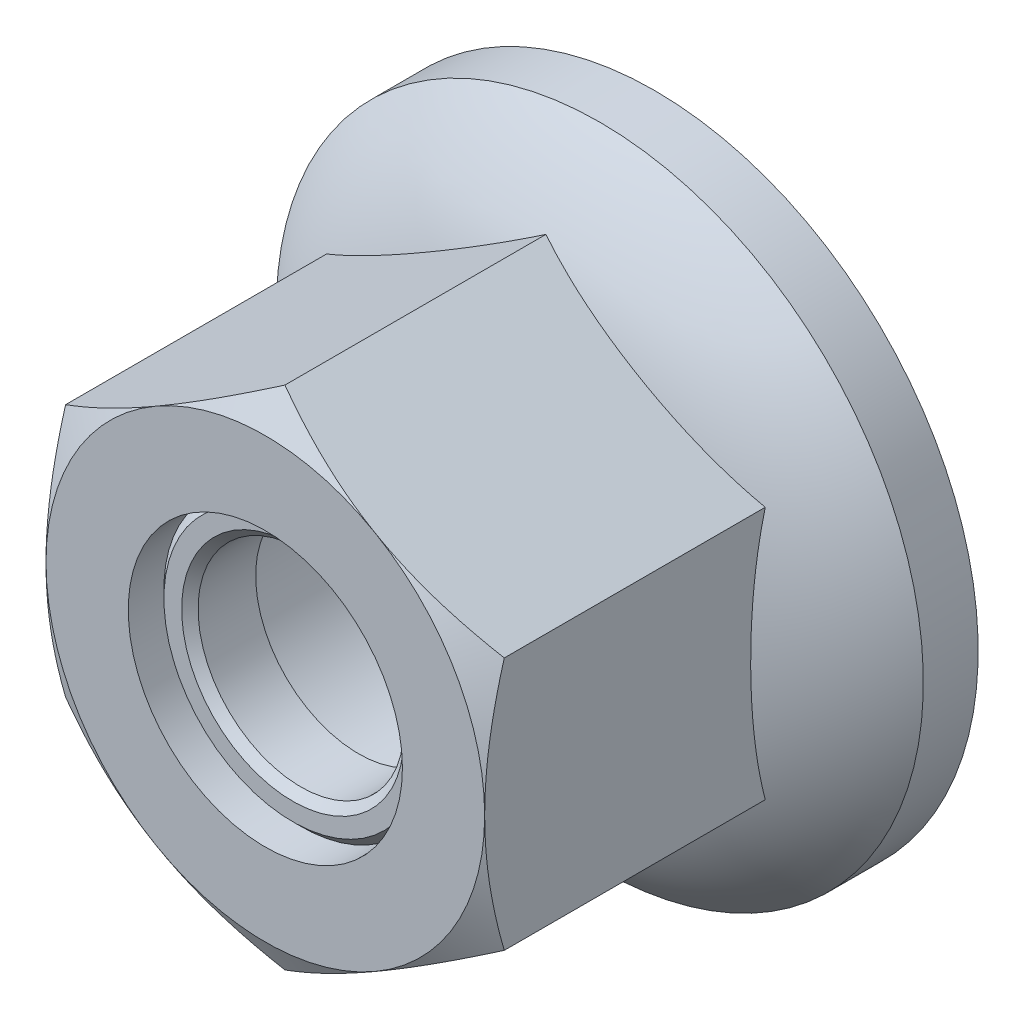
SolidWorks part; units mm, degrees
material "Alloy Steel"
ref_plane "Front Plane" through (0, 0, 0) normal (0, 0, 1) x (1, 0, 0)
ref_plane "Top Plane" through (0, 0, 0) normal (0, 1, 0) x (1, 0, 0)
ref_plane "Right Plane" through (0, 0, 0) normal (1, 0, 0) x (0, 0, -1)
sketch "Sketch1" plane through (0, 0, 0) normal (0, 0, 1) x (1, 0, 0)
  line L1 (0, 4.6188) -> (-4, 2.3094)
  line L2 (-4, 2.3094) -> (-4, -2.3094)
  line L3 (-4, -2.3094) -> (0, -4.6188)
  line L4 (0, -4.6188) -> (4, -2.3094)
  line L5 (4, -2.3094) -> (4, 2.3094)
  line L6 (4, 2.3094) -> (0, 4.6188)
  circle A0 centre (0, 0) radius 4 construction
  circle A1 centre (0, 0) radius 2.5
  dimension "Thread Size" = 5
  dimension "Hex" = 8
extrude "Extrude1" add sketch "Sketch1" against normal blind 7.1
sketch "Sketch2" plane through (0, 0, 0) normal (0, 0, 1) x (1, 0, 0)
  circle A0 centre (0, 0) radius 4 construction
  circle A1 centre (0, 0) radius 4
extrude "Cut-Extrude1" cut sketch "Sketch2" against normal through all draft 60 flip side to cut
sketch "Sketch3" plane through (0, 0, 0) normal (1, 0, 0) x (0, 0, -1)
  line L0 (7.1, 5.9) -> (7.1, 2.5)
  line L1 (7.1, 2.5) -> (4.6, 2.5)
  line L2 (7.1, 5.9) -> (6.1, 5.9)
  line L3 (0, 0) -> (7.1, 0) construction
  line L4 (0, -2.3094) -> (0, 2.3094) construction
  line L5 (7.1, -2.3094) -> (7.1, 2.3094) construction
  line L6 (7.1, 2.3094) -> (7.1, 4.6188) construction
  line L7 (7.1, -2.5) -> (7.1, 2.5) construction
  line L8 (4.6, 2.5) -> (4.6, 5.9) construction
  arc A0 (6.1, 5.9) -> (4.6, 2.5) centre (9.2033, 2.5) ccw
  dimension "Flange OD" = 11.8
  dimension "Flange Thickness" = 1
  dimension "D1" = 1.5
revolve "Revolve1" add sketch "Sketch3" angle 360 about L3
sketch "Sketch5" plane through (0, 0, 0) normal (0, 0, 1) x (1, 0, 0)
  circle A1 centre (0, 0) radius 2.5
  circle A2 centre (0, 0) radius 2.5 construction
curve "Helix/Spiral1" [suppressed] pitch 0.8 height 7.9 turns 9.875 parameters "pitch"=0.8
sketch "Sketch10" plane through (0, 0, 0) normal (0, 0, 1) x (1, 0, 0)
  circle A1 centre (0, 0) radius 2.5 construction
  circle A2 centre (0, 0) radius 1.8765
  circle A3 centre (0, 0) radius 1.8765
  circle A4 centre (0, 0) radius 2.5
  dimension "D1" = 0.6235
extrude "Boss-Extrude1" add sketch "Sketch10" against normal blind 1.2 from offset 0.5 separate body offset against normal yes
chamfer "Chamfer1" distance 0.15 angle 45 2 edges at (2.5, 0, -0.5) (1.8765, 0, -0.5)
sketch "Sketch6" [suppressed] plane through (0, 0, 0) normal (1, 0, 0) x (0, 0, -1)
  line L0 (-0.7, 2.5) -> (0, 2.5)
  line L1 (-0.7, 2.5) -> (-0.4, 1.9804)
  line L2 (-0.4, 1.9804) -> (-0.3, 1.9804)
  line L3 (-0.3, 1.9804) -> (0, 2.5)
  line L4 (-0.35, 1.9804) -> (-0.35, 2.5) construction
  line L5 (-0.55, 2.2402) -> (-0.15, 2.2402) construction
  dimension "D1" = 60
  dimension "D2" = 0.1
  dimension "D3" = 0.4
  dimension "D4" = 0.5196
sweep "Sweep1" [suppressed] add profiles "Sketch6" path "Helix/Spiral1"
sketch "Sketch7" [suppressed] plane through (0, 0, -1.7) normal (0, 0, 1) x (1, 0, 0)
  circle A1 centre (0, 0) radius 2.5
  circle A2 centre (0, 0) radius 2.5
  dimension "D1" = 0
extrude "Cut-Extrude2" [suppressed] cut sketch "Sketch7" against normal through all draft 45 and the other way through all
sketch "Sketch8" [suppressed] plane through (0, 0, -7.1) normal (0, 0, -1) x (-1, 0, 0)
  circle A1 centre (0, 0) radius 2.5
  circle A2 centre (0, 0) radius 2.5
  dimension "D1" = 0
extrude "Cut-Extrude3" [suppressed] cut sketch "Sketch8" against normal through all draft 45 and the other way through all draft 45
ref_axis "Center Axis 1" [suppressed] through (0, 0, -8.701) along (0, 0, 1)
ref_plane "Contact Plane 1" [suppressed] through (0, 0, -7.1) normal (0, 0, -1) x (-1, 0, 0)
equation "\"D3@Helix/Spiral1\" = \"pitch@Helix/Spiral1\"+\"Height@Extrude1\""
equation "\"D2@Sketch6\"=\"pitch@Helix/Spiral1\"*.125"
equation "\"D3@Sketch6\"=\"pitch@Helix/Spiral1\"*.50"
equation "\"D1@Sketch10\"=\"D4@Sketch6\"*1.2"
equation "\"D1@Boss-Extrude1\"=\"pitch@Helix/Spiral1\"*1.5"
equation "\"D1@Sketch3\"=\"Flange Thickness@Sketch3\"*1.5"
